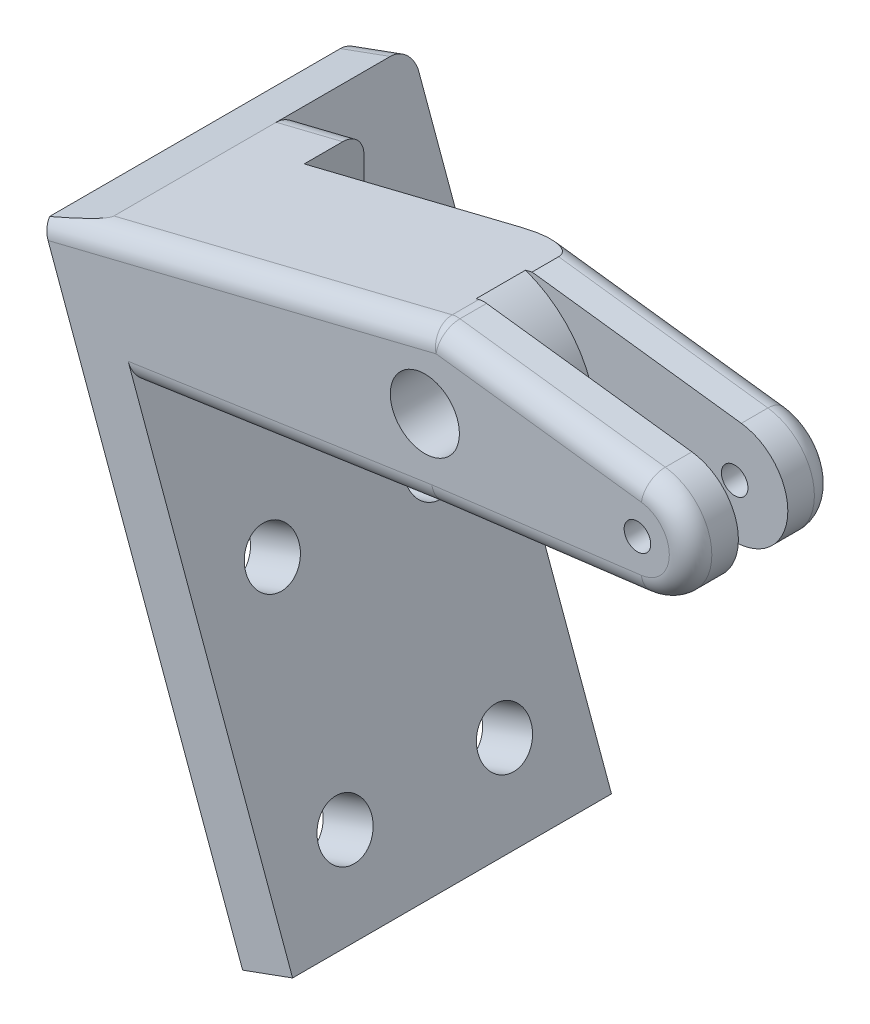
SolidWorks part; units mm, degrees
ref_plane "Front Plane" through (0, 0, 0) normal (0, 0, 1) x (1, 0, 0)
ref_plane "Top Plane" through (0, 0, 0) normal (0, 1, 0) x (1, 0, 0)
ref_plane "Right Plane" through (0, 0, 0) normal (1, 0, 0) x (0, 0, -1)
sketch "Sketch1" plane through (0, 0, 0) normal (0, 0, 1) x (1, 0, 0)
  line L0 (-61.0118, 0) -> (20, 0) construction
  line L1 (-29.5442, -5.2094) -> (0, 0) construction
  line L2 (20.625, 4.9608) -> (0.9375, 7.4412)
  line L3 (20.625, -4.9608) -> (0.9375, -7.4412)
  line L4 (-27.2185, -11.5994) -> (-12.4432, -52.1941)
  line L5 (-29.5442, -5.2094) -> (-31.2543, -0.511) construction
  line L6 (-31.2543, -0.511) -> (0.9375, 7.4412)
  line L7 (-27.2185, -11.5994) -> (0.9375, -7.4412)
  line L8 (-31.2543, -0.511) -> (-35.9528, -2.2211)
  line L9 (-35.9528, -2.2211) -> (-17.1417, -53.9042)
  line L10 (-17.1417, -53.9042) -> (-12.4432, -52.1941)
  circle A0 centre (0, 0) radius 3.25
  circle A1 centre (20, 0) radius 1.25
  circle A2 centre (0, 0) radius 7.5 construction
  arc A3 (20.625, -4.9608) -> (20.625, 4.9608) centre (20, 0) ccw
  dimension "D3" = 6.5
  dimension "D4" = 2.5
  dimension "D6" = 10
  dimension "D7" = 15
  dimension "D8" = 80
  dimension "D1" = 20
  dimension "D2" = 10
  dimension "D5" = 30
  dimension "D9" = 5
  dimension "D10" = 50
  dimension "D11" = 6.8
  dimension "D12" = 5
extrude "Boss-Extrude1" add sketch "Sketch1" along normal blind 30
sketch "Sketch2" plane through (0, 0, 0) normal (1, 0, 0) x (0, 0, -1)
  line L0 (0, 0) -> (-30, 0) construction
  line L1 (-30, 4.9608) -> (-30, -4.9608) construction
  line L2 (-30, -7.4412) -> (-30, -4.9608) construction
  line L3 (-25.5, 15.5349) -> (-20.85, 15.5349)
  line L4 (-25.5, 15.5349) -> (-25.5, -15.5349)
  line L5 (-25.5, -15.5349) -> (-20.85, -15.5349)
  line L6 (-20.85, 15.5349) -> (-20.85, -15.5349)
  line L7 (-25.5, 15.5349) -> (-20.85, -15.5349) construction
  line L8 (-25.5, -15.5349) -> (-20.85, 15.5349) construction
  point P6 (-23.175, 0)
  dimension "D1" = 4.5
  dimension "D2" = 4.65
extrude "Cut-Extrude2" cut sketch "Sketch2" along normal blind 50 from offset 7 contours L6 L3 L4 L5 region at (0, 0, 23.175)
sketch "Sketch3" plane through (0, 0, 0) normal (1, 0, 0) x (0, 0, -1)
  line L0 (0, 0) -> (-30, 0) construction
  line L1 (-30, 4.9608) -> (-30, -4.9608) construction
  line L2 (0, -52.1941) -> (0, -11.5994) construction
  line L3 (-16.35, 15.6057) -> (0, 15.6057)
  line L4 (-16.35, 15.6057) -> (-16.35, -15.6057)
  line L5 (-16.35, -15.6057) -> (0, -15.6057)
  line L6 (0, 15.6057) -> (0, -15.6057)
  line L7 (-16.35, 15.6057) -> (0, -15.6057) construction
  line L8 (-16.35, -15.6057) -> (0, 15.6057) construction
  line L9 (-20.85, 4.9608) -> (-20.85, -4.9608) construction
  point P5 (-8.175, 0)
  dimension "D1" = 4.5
extrude "Cut-Extrude3" cut sketch "Sketch3" against normal blind 25 and the other way blind 50
sketch "Sketch4" plane through (0, 0, 0) normal (0, 0, 1) x (1, 0, 0)
  line L0 (-27.2185, -11.5994) -> (-32.993, 4.2658)
  line L1 (-32.993, 4.2658) -> (-19.614, 7.8545)
  line L2 (-19.614, 7.8545) -> (-19.614, -14.9588)
  line L3 (-19.614, -14.9588) -> (-27.2185, -11.5994)
extrude "Cut-Extrude4" cut sketch "Sketch4" along normal blind 10.73
fillet "Fillet1" radius 10 1 edges at (7, 6.6774, 23.175)
fillet "Fillet2" radius 2 4 edges at (10.7813, 6.201, 16.35) (25, 0, 16.35) (10.7812, -6.201, 16.35) (-12.0312, -9.3564, 16.35)
fillet "Fillet3" radius 2 1 edges at (-28.1272, 0.2615, 10.73)
fillet "Fillet6" radius 2 3 edges at (-26.1092, -11.4355, 10.73) (-33.6036, -1.366, 0) (-15.1584, 3.4651, 30)
fillet "Fillet8" radius 2 6 edges at (0.9375, 7.4412, 26.75) (2.5551, 7.2374, 29.4142) (13.5427, 5.8531, 30) (25, 0, 30) (10.7813, -6.201, 30) (-13.1405, -9.5203, 30)
fillet "Fillet9" radius 2 1 edges at (7, -6.6774, 23.175)
scale "缩放比例1" scale about centroid uniform scaling yes scale factor 2
sketch "草图2" plane through (-46.3321, -16.8635, 0) normal (-0.9397, -0.342, 0) x (0, 0, 1)
  line L0 (11.1632, -80.9448) -> (11.1632, 74.9682) construction
  line L1 (41.1632, -80.9448) -> (-18.8368, -80.9448) construction
  circle A0 centre (26.1632, -65.9448) radius 5
  circle A1 centre (26.1632, -25.9448) radius 5
  circle A2 centre (-3.8368, -25.9448) radius 5
  circle A3 centre (-3.8368, -65.9448) radius 5
  point P10 (27.2006, -63.151)
  point P11 (27.2006, -64.1255)
  dimension "D1" = 10
  dimension "D2" = 10
  dimension "D3" = 15
  dimension "D4" = 15
  dimension "D5" = 40
  dimension "D6" = 15
extrude "切除-拉伸2" cut sketch "草图2" against normal blind 20
